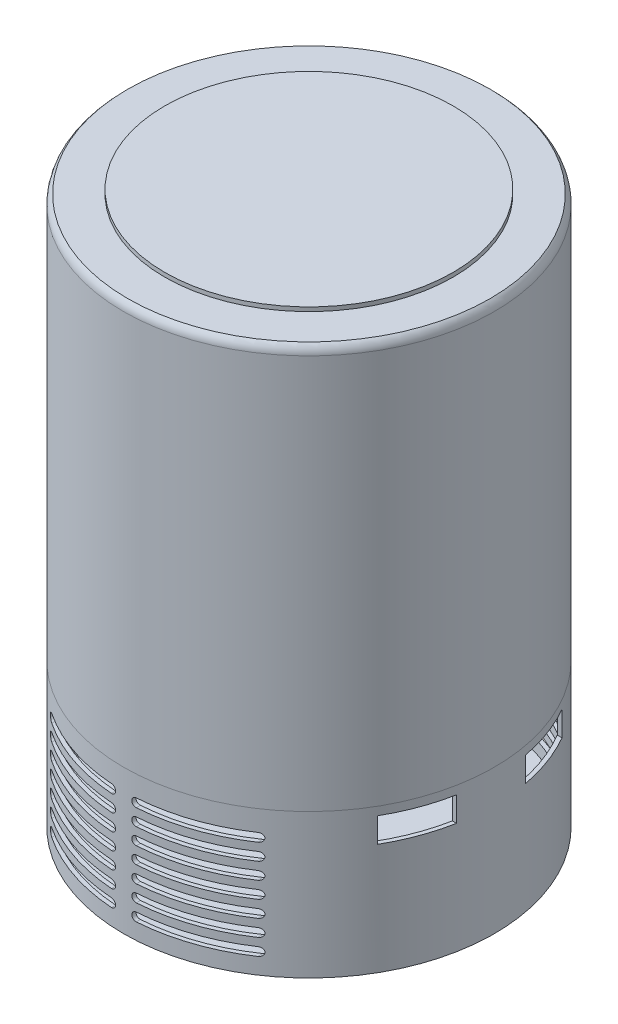
SolidWorks part; units mm, degrees
ref_plane "Front Plane" through (0, 0, 0) normal (0, 0, 1) x (1, 0, 0)
ref_plane "Top Plane" through (0, 0, 0) normal (0, 1, 0) x (1, 0, 0)
ref_plane "Right Plane" through (0, 0, 0) normal (1, 0, 0) x (0, 0, -1)
sketch "Sketch1" plane through (0, 0, 0) normal (0, 1, 0) x (1, 0, 0)
  circle A0 centre (0, 0) radius 45
  circle A1 centre (0, 0) radius 44
  dimension "D1" = 90
  dimension "D2" = 88
extrude "Boss-Extrude1" add sketch "Sketch1" along normal blind 98
fillet "Fillet1" radius 3 1 edges at (0, 98, 45)
sketch "Sketch13" plane through (0, 0, 0) normal (0, 1, 0) x (1, 0, 0)
  circle A0 centre (0, 0) radius 44
  dimension "D1" = 88
extrude "Boss-Extrude9" add sketch "Sketch13" along normal blind 2 from offset 96
sketch "Sketch5" plane through (0, 0, 0) normal (0, 1, 0) x (1, 0, 0)
  circle A0 centre (0, 0) radius 45
  dimension "D1" = 90
extrude "Boss-Extrude6" add sketch "Sketch5" against normal blind 35 separate body
sketch "Sketch6" plane through (0, 0, 0) normal (0, 1, 0) x (1, 0, 0)
  circle A0 centre (0, 0) radius 44
  dimension "D1" = 88
extrude "Cut-Extrude2" cut sketch "Sketch6" against normal blind 34
sketch "Sketch7" plane through (0, 98, 0) normal (0, 1, 0) x (1, 0, 0)
  circle A0 centre (0, 0) radius 35
  dimension "D1" = 70
extrude "Boss-Extrude7" add sketch "Sketch7" along normal blind 1
sketch "Sketch8" plane through (0, 0, 0) normal (1, 0, 0) x (0, 0, -1)
  line L0 (45, -17.5) -> (-47.6224, -17.5) construction
  line L1 (45, -35) -> (45, 0) construction
  line L3 (4, -5.5) -> (-4, -5.5)
  line L4 (4, -5.5) -> (4, -2)
  line L5 (4, -2) -> (-4, -2)
  line L6 (-4, -5.5) -> (-4, -2)
  line L7 (4, -5.5) -> (-4, -2) construction
  line L8 (4, -2) -> (-4, -5.5) construction
  line L10 (44, 0) -> (-44, 0) construction
  point P4 (0, -3.75)
  dimension "D1" = 8
  dimension "D2" = 3.5
  dimension "D3" = 2
extrude "Cut-Extrude3" cut sketch "Sketch8" against normal through all from offset 39 offset against normal yes
sketch "Sketch10" plane through (0, 0, 0) normal (0, 0, 1) x (1, 0, 0)
  line L0 (25, -6.0288) -> (3, -6.0288) construction
  line L5 (0, 12.9357) -> (0, -57.2827) construction
  line L30 (25, -5) -> (3, -5)
  line L31 (25, -7.0576) -> (3, -7.0576)
  line L32 (-25, -6.0288) -> (-3, -6.0288) construction
  line L33 (-25, -5) -> (-3, -5)
  line L34 (-25, -7.0576) -> (-3, -7.0576)
  line L35 (-25, -10.0288) -> (-3, -10.0288) construction
  line L36 (-25, -9) -> (-3, -9)
  line L37 (-25, -11.0576) -> (-3, -11.0576)
  line L38 (25, -10.0288) -> (3, -10.0288) construction
  line L39 (25, -9) -> (3, -9)
  line L40 (25, -11.0576) -> (3, -11.0576)
  line L41 (-25, -14.0288) -> (-3, -14.0288) construction
  line L42 (-25, -13) -> (-3, -13)
  line L43 (-25, -15.0576) -> (-3, -15.0576)
  line L44 (25, -14.0288) -> (3, -14.0288) construction
  line L45 (25, -13) -> (3, -13)
  line L46 (25, -15.0576) -> (3, -15.0576)
  line L47 (-25, -18.0288) -> (-3, -18.0288) construction
  line L48 (-25, -17) -> (-3, -17)
  line L49 (-25, -19.0576) -> (-3, -19.0576)
  line L50 (25, -18.0288) -> (3, -18.0288) construction
  line L51 (25, -17) -> (3, -17)
  line L52 (25, -19.0576) -> (3, -19.0576)
  line L53 (-25, -22.0288) -> (-3, -22.0288) construction
  line L54 (-25, -21) -> (-3, -21)
  line L55 (-25, -23.0576) -> (-3, -23.0576)
  line L56 (25, -22.0288) -> (3, -22.0288) construction
  line L57 (25, -21) -> (3, -21)
  line L58 (25, -23.0576) -> (3, -23.0576)
  line L59 (-25, -26.0288) -> (-3, -26.0288) construction
  line L60 (-25, -25) -> (-3, -25)
  line L61 (-25, -27.0576) -> (-3, -27.0576)
  line L62 (25, -26.0288) -> (3, -26.0288) construction
  line L63 (25, -25) -> (3, -25)
  line L64 (25, -27.0576) -> (3, -27.0576)
  line L65 (45, 0) -> (-45, 0) construction
  line L66 (-25, -30.0288) -> (-3, -30.0288) construction
  line L67 (-25, -29) -> (-3, -29)
  line L68 (-25, -31.0576) -> (-3, -31.0576)
  line L69 (-14, -8.33) -> (-14, -41.8813) construction
  line L70 (25, -30.0288) -> (3, -30.0288) construction
  line L71 (25, -29) -> (3, -29)
  line L72 (25, -31.0576) -> (3, -31.0576)
  arc A0 (-25, -5) -> (-25, -7.0576) centre (-25, -6.0288) ccw
  arc A1 (-3, -7.0576) -> (-3, -5) centre (-3, -6.0288) ccw
  arc A2 (25, -5) -> (25, -7.0576) centre (25, -6.0288) cw
  arc A3 (3, -7.0576) -> (3, -5) centre (3, -6.0288) cw
  arc A4 (-25, -9) -> (-25, -11.0576) centre (-25, -10.0288) ccw
  arc A5 (-3, -11.0576) -> (-3, -9) centre (-3, -10.0288) ccw
  arc A6 (25, -9) -> (25, -11.0576) centre (25, -10.0288) cw
  arc A7 (3, -11.0576) -> (3, -9) centre (3, -10.0288) cw
  arc A8 (-25, -13) -> (-25, -15.0576) centre (-25, -14.0288) ccw
  arc A9 (-3, -15.0576) -> (-3, -13) centre (-3, -14.0288) ccw
  arc A10 (25, -13) -> (25, -15.0576) centre (25, -14.0288) cw
  arc A11 (3, -15.0576) -> (3, -13) centre (3, -14.0288) cw
  arc A12 (-25, -17) -> (-25, -19.0576) centre (-25, -18.0288) ccw
  arc A13 (-3, -19.0576) -> (-3, -17) centre (-3, -18.0288) ccw
  arc A14 (25, -17) -> (25, -19.0576) centre (25, -18.0288) cw
  arc A15 (3, -19.0576) -> (3, -17) centre (3, -18.0288) cw
  arc A16 (-25, -21) -> (-25, -23.0576) centre (-25, -22.0288) ccw
  arc A17 (-3, -23.0576) -> (-3, -21) centre (-3, -22.0288) ccw
  arc A18 (25, -21) -> (25, -23.0576) centre (25, -22.0288) cw
  arc A19 (3, -23.0576) -> (3, -21) centre (3, -22.0288) cw
  arc A20 (-25, -25) -> (-25, -27.0576) centre (-25, -26.0288) ccw
  arc A21 (-3, -27.0576) -> (-3, -25) centre (-3, -26.0288) ccw
  arc A22 (25, -25) -> (25, -27.0576) centre (25, -26.0288) cw
  arc A23 (3, -27.0576) -> (3, -25) centre (3, -26.0288) cw
  arc A24 (-25, -29) -> (-25, -31.0576) centre (-25, -30.0288) ccw
  arc A25 (-3, -31.0576) -> (-3, -29) centre (-3, -30.0288) ccw
  arc A26 (25, -29) -> (25, -31.0576) centre (25, -30.0288) cw
  arc A27 (3, -31.0576) -> (3, -29) centre (3, -30.0288) cw
  point P3 (14, -6.0288)
  point P7 (-14, -6.0288)
  point P19 (14, -10.0288)
  point P22 (-14, -10.0288)
  point P33 (14, -14.0288)
  point P36 (-14, -14.0288)
  point P47 (14, -18.0288)
  point P50 (-14, -18.0288)
  point P61 (14, -22.0288)
  point P64 (-14, -22.0288)
  point P75 (14, -26.0288)
  point P78 (-14, -26.0288)
  point P90 (-14, -30.0288)
  point P101 (14, -30.0288)
  dimension "D1" = 22
  dimension "D2" = 6
  dimension "D3" = 5
  dimension "D5" = 1.9424
  dimension "D4" = 1.9424
extrude "Cut-Extrude5" cut sketch "Sketch10" against normal blind 10 from offset 36 offset against normal yes
sketch "Sketch12" plane through (0, 0, 0) normal (0, 0, 1) x (1, 0, 0)
  line L0 (25, -6.0288) -> (3, -6.0288) construction
  line L5 (0, 12.9357) -> (0, -57.2827) construction
  line L30 (25, -5) -> (3, -5)
  line L31 (25, -7.0576) -> (3, -7.0576)
  line L32 (-25, -6.0288) -> (-3, -6.0288) construction
  line L33 (-25, -5) -> (-3, -5)
  line L34 (-25, -7.0576) -> (-3, -7.0576)
  line L35 (-25, -10.0288) -> (-3, -10.0288) construction
  line L36 (-25, -9) -> (-3, -9)
  line L37 (-25, -11.0576) -> (-3, -11.0576)
  line L38 (25, -10.0288) -> (3, -10.0288) construction
  line L39 (25, -9) -> (3, -9)
  line L40 (25, -11.0576) -> (3, -11.0576)
  line L41 (-25, -14.0288) -> (-3, -14.0288) construction
  line L42 (-25, -13) -> (-3, -13)
  line L43 (-25, -15.0576) -> (-3, -15.0576)
  line L44 (25, -14.0288) -> (3, -14.0288) construction
  line L45 (25, -13) -> (3, -13)
  line L46 (25, -15.0576) -> (3, -15.0576)
  line L47 (-25, -18.0288) -> (-3, -18.0288) construction
  line L48 (-25, -17) -> (-3, -17)
  line L49 (-25, -19.0576) -> (-3, -19.0576)
  line L50 (25, -18.0288) -> (3, -18.0288) construction
  line L51 (25, -17) -> (3, -17)
  line L52 (25, -19.0576) -> (3, -19.0576)
  line L53 (-25, -22.0288) -> (-3, -22.0288) construction
  line L54 (-25, -21) -> (-3, -21)
  line L55 (-25, -23.0576) -> (-3, -23.0576)
  line L56 (25, -22.0288) -> (3, -22.0288) construction
  line L57 (25, -21) -> (3, -21)
  line L58 (25, -23.0576) -> (3, -23.0576)
  line L59 (-25, -26.0288) -> (-3, -26.0288) construction
  line L60 (-25, -25) -> (-3, -25)
  line L61 (-25, -27.0576) -> (-3, -27.0576)
  line L62 (25, -26.0288) -> (3, -26.0288) construction
  line L63 (25, -25) -> (3, -25)
  line L64 (25, -27.0576) -> (3, -27.0576)
  line L65 (45, 0) -> (-45, 0) construction
  line L66 (-25, -29) -> (-3, -29) construction
  line L67 (-25, -29) -> (-3, -29)
  line L68 (-25, -31.0576) -> (-3, -31.0576) construction
  line L69 (-25, -31.0576) -> (-3, -31.0576)
  line L70 (25, -31.0576) -> (3, -31.0576) construction
  line L71 (25, -29) -> (3, -29) construction
  line L72 (25, -31.0576) -> (3, -31.0576)
  line L73 (25, -29) -> (3, -29)
  arc A0 (-25, -5) -> (-25, -7.0576) centre (-25, -6.0288) ccw
  arc A1 (-3, -7.0576) -> (-3, -5) centre (-3, -6.0288) ccw
  arc A2 (25, -5) -> (25, -7.0576) centre (25, -6.0288) cw
  arc A3 (3, -7.0576) -> (3, -5) centre (3, -6.0288) cw
  arc A4 (-25, -9) -> (-25, -11.0576) centre (-25, -10.0288) ccw
  arc A5 (-3, -11.0576) -> (-3, -9) centre (-3, -10.0288) ccw
  arc A6 (25, -9) -> (25, -11.0576) centre (25, -10.0288) cw
  arc A7 (3, -11.0576) -> (3, -9) centre (3, -10.0288) cw
  arc A8 (-25, -13) -> (-25, -15.0576) centre (-25, -14.0288) ccw
  arc A9 (-3, -15.0576) -> (-3, -13) centre (-3, -14.0288) ccw
  arc A10 (25, -13) -> (25, -15.0576) centre (25, -14.0288) cw
  arc A11 (3, -15.0576) -> (3, -13) centre (3, -14.0288) cw
  arc A12 (-25, -17) -> (-25, -19.0576) centre (-25, -18.0288) ccw
  arc A13 (-3, -19.0576) -> (-3, -17) centre (-3, -18.0288) ccw
  arc A14 (25, -17) -> (25, -19.0576) centre (25, -18.0288) cw
  arc A15 (3, -19.0576) -> (3, -17) centre (3, -18.0288) cw
  arc A16 (-25, -21) -> (-25, -23.0576) centre (-25, -22.0288) ccw
  arc A17 (-3, -23.0576) -> (-3, -21) centre (-3, -22.0288) ccw
  arc A18 (25, -21) -> (25, -23.0576) centre (25, -22.0288) cw
  arc A19 (3, -23.0576) -> (3, -21) centre (3, -22.0288) cw
  arc A20 (-25, -25) -> (-25, -27.0576) centre (-25, -26.0288) ccw
  arc A21 (-3, -27.0576) -> (-3, -25) centre (-3, -26.0288) ccw
  arc A22 (25, -25) -> (25, -27.0576) centre (25, -26.0288) cw
  arc A23 (3, -27.0576) -> (3, -25) centre (3, -26.0288) cw
  arc A24 (-3, -31.0576) -> (-3, -29) centre (-3, -30.0288) ccw construction
  arc A25 (-25, -29) -> (-25, -31.0576) centre (-25, -30.0288) ccw construction
  arc A26 (-3, -31.0576) -> (-3, -29) centre (-3, -30.0288) ccw
  arc A27 (-25, -29) -> (-25, -31.0576) centre (-25, -30.0288) ccw
  arc A28 (25, -31.0576) -> (25, -29) centre (25, -30.0288) ccw construction
  arc A29 (3, -29) -> (3, -31.0576) centre (3, -30.0288) ccw construction
  arc A30 (25, -31.0576) -> (25, -29) centre (25, -30.0288) ccw
  arc A31 (3, -29) -> (3, -31.0576) centre (3, -30.0288) ccw
  point P3 (14, -6.0288)
  point P7 (-14, -6.0288)
  point P19 (14, -10.0288)
  point P22 (-14, -10.0288)
  point P33 (14, -14.0288)
  point P36 (-14, -14.0288)
  point P47 (14, -18.0288)
  point P50 (-14, -18.0288)
  point P61 (14, -22.0288)
  point P64 (-14, -22.0288)
  point P75 (14, -26.0288)
  point P78 (-14, -26.0288)
  dimension "D1" = 22
  dimension "D2" = 6
  dimension "D3" = 5
extrude "Cut-Extrude6" cut sketch "Sketch12" against normal blind 10 from offset 46
sketch "Sketch15" [suppressed] plane through (0, 0, 0) normal (0, 1, 0) x (1, 0, 0)
  line L0 (-48.3245, 0) -> (49.2947, 0) construction
  line L1 (0, 0) -> (42.2862, -15.3909)
  line L2 (0, 0) -> (42.2862, 15.3909)
  circle A0 centre (0, 0) radius 45 construction
  dimension "D1" = 20
sketch "Sketch14" plane through (0, 0, 0) normal (1, 0, 0) x (0, 0, -1)
  line L0 (-47.6224, -17.5) -> (48.7265, -17.5) construction
  line L2 (-8.3909, -8) -> (-22.3909, -8)
  line L3 (-8.3909, -8) -> (-8.3909, -2)
  line L4 (-8.3909, -2) -> (-22.3909, -2)
  line L5 (-22.3909, -8) -> (-22.3909, -2)
  line L6 (-8.3909, -8) -> (-22.3909, -2) construction
  line L7 (-8.3909, -2) -> (-22.3909, -8) construction
  line L8 (22.3909, -8) -> (8.3909, -8)
  line L9 (22.3909, -8) -> (22.3909, -2)
  line L10 (22.3909, -2) -> (8.3909, -2)
  line L11 (8.3909, -8) -> (8.3909, -2)
  line L12 (22.3909, -8) -> (8.3909, -2) construction
  line L13 (22.3909, -2) -> (8.3909, -8) construction
  line L16 (-44, 0) -> (44, 0) construction
  line L17 (0, 16.6073) -> (0, -22.4392) construction
  line L19 (-15.3909, 7.2444) -> (-15.3909, -11.5076) construction
  line L20 (15.3909, 7.2444) -> (15.3909, -11.5076) construction
  point P3 (-15.3909, -5)
  point P8 (15.3909, -5)
  point P26 (-15.3909, -2)
  dimension "D1" = 14
  dimension "D2" = 6
  dimension "D3" = 14
  dimension "D4" = 6
  dimension "D7" = 2
  dimension "D8" = 2
extrude "Cut-Extrude7" cut sketch "Sketch14" along normal blind 10 from offset 36
